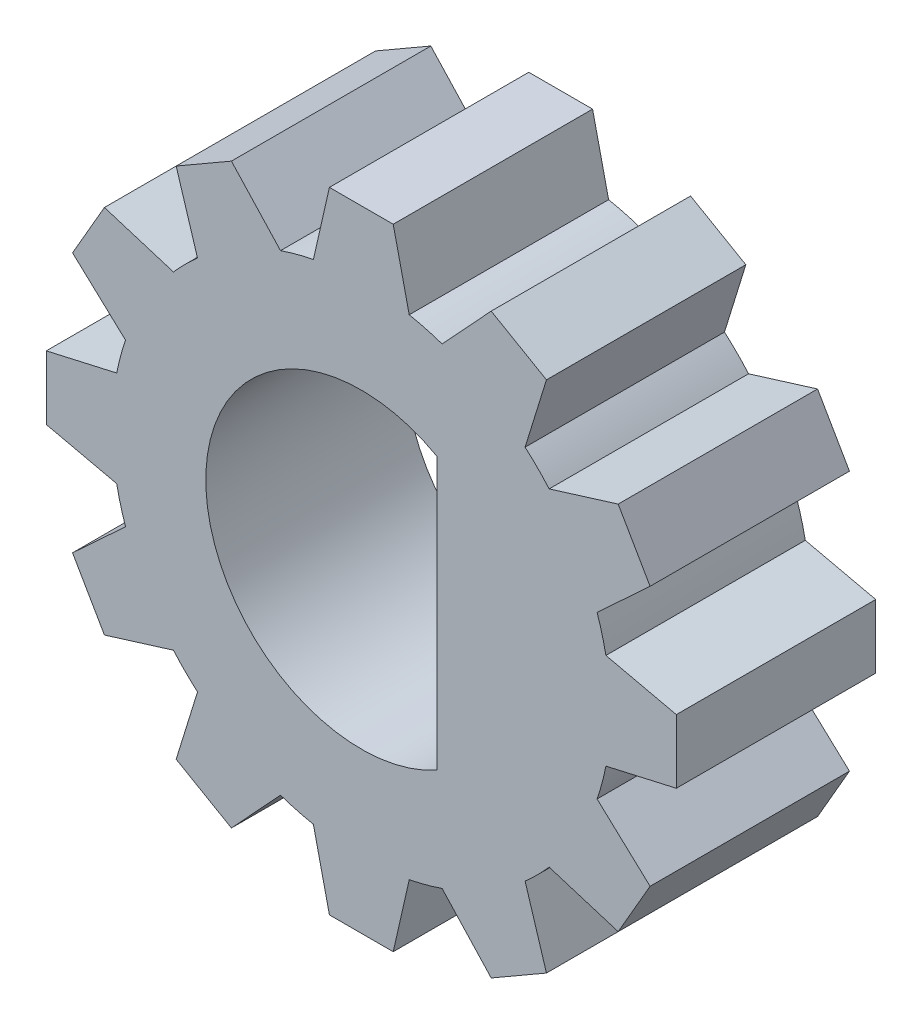
SolidWorks part; units mm, degrees
ref_plane "Front Plane" through (0, 0, 0) normal (0, 0, 1) x (1, 0, 0)
ref_plane "Top Plane" through (0, 0, 0) normal (0, 1, 0) x (1, 0, 0)
ref_plane "Right Plane" through (0, 0, 0) normal (1, 0, 0) x (0, 0, -1)
sketch "Sketch1" plane through (0, 0, 0) normal (0, 0, 1) x (1, 0, 0)
  circle A0 centre (0, 0) radius 6.25
  dimension "D1" = 12.5
extrude "Boss-Extrude1" add sketch "Sketch1" along normal blind 5
sketch "Sketch3" plane through (0, 0, 0) normal (0, 0, 1) x (1, 0, 0)
  line L0 (0, -7.9) -> (0, 7.9) construction
  line L1 (-0.8, 7.9) -> (0.8, 7.9)
  line L2 (-0.8, 7.9) -> (-1.3, 5.7)
  line L3 (-1.3, 5.7) -> (1.3, 5.7)
  line L4 (1.3, 5.7) -> (0.8, 7.9)
  point P3 (0, 0)
  point P4 (0, 5.7)
  point P6 (0, 7.9)
  dimension "D1" = 7.9
  dimension "D2" = 2.6
  dimension "D3" = 1.6
  dimension "D4" = 5.7
extrude "Boss-Extrude2" add sketch "Sketch3" along normal blind 5
ref_axis "Axis2" through (0, 0, 5) along (0, 0, -1)
pattern_circular "CirPattern1" count 12 every 30 about axis through (0, 0, 0) along (0, 0, 1) of "Boss-Extrude2"
sketch "Sketch4" plane through (0, 0, 0) normal (0, 0, 1) x (1, 0, 0)
  line L0 (1.9, 3.4059) -> (1.9, -3.4059)
  arc A0 (1.9, 3.4059) -> (1.9, -3.4059) centre (0, 0) ccw
  dimension "D1" = 7.8
  dimension "D2" = 1.9
extrude "Cut-Extrude1" cut sketch "Sketch4" along normal blind 7
